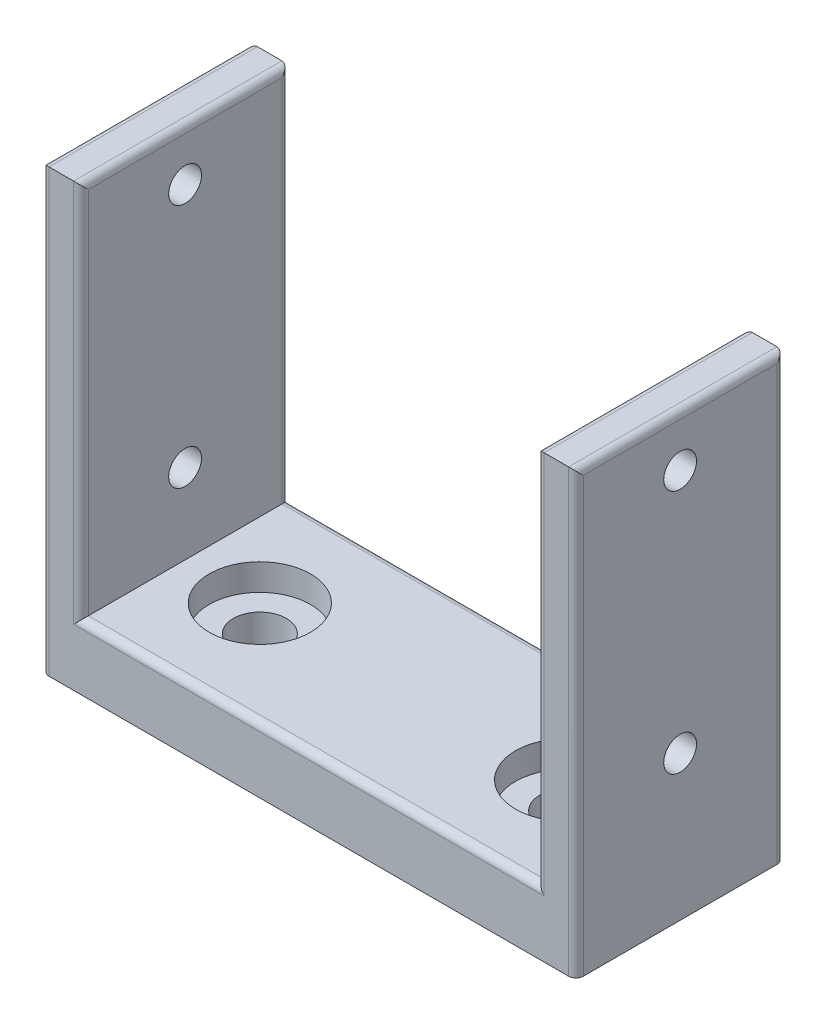
SolidWorks part; units mm, degrees
ref_plane "Front Plane" through (0, 0, 0) normal (0, 0, 1) x (1, 0, 0)
ref_plane "Top Plane" through (0, 0, 0) normal (0, 1, 0) x (1, 0, 0)
ref_plane "Right Plane" through (0, 0, 0) normal (1, 0, 0) x (0, 0, -1)
sketch "Sketch1" plane through (0, 0, 0) normal (0, 1, 0) x (1, 0, 0)
  line L1 (0, 21.59) -> (55.372, 21.59)
  line L2 (0, 21.59) -> (0, 0)
  line L3 (0, 0) -> (55.372, 0)
  line L4 (55.372, 21.59) -> (55.372, 0)
  dimension "D1" = 55.372
  dimension "D2" = 21.59
extrude "Boss-Extrude1" add sketch "Sketch1" along normal blind 4.16
sketch "Sketch2" plane through (0, 4.16, 0) normal (0, 1, 0) x (1, 0, 0)
  line L0 (0, 0) -> (55.372, 0) construction
  line L1 (0, 21.59) -> (4.064, 21.59)
  line L2 (0, 21.59) -> (0, 0)
  line L3 (0, 0) -> (4.064, 0)
  line L4 (4.064, 21.59) -> (4.064, 0)
  line L6 (55.372, 21.59) -> (51.308, 21.59)
  line L7 (55.372, 21.59) -> (55.372, 0)
  line L8 (55.372, 0) -> (51.308, 0)
  line L9 (51.308, 21.59) -> (51.308, 0)
  dimension "D1" = 4.064
  dimension "D2" = 4.064
extrude "Boss-Extrude2" add sketch "Sketch2" along normal blind 39.02
hole_wizard "M3 Clearance Hole2" positions "Sketch5" profile "Sketch4" hole size "M3" standard "ANSI Metric" end condition through all
sketch "Sketch5" plane through (0, 0, 0) normal (-1, 0, 0) x (0, 0, 1)
  line L0 (-21.59, 43.18) -> (0, 43.18) construction
  point P0 (-10.795, 37.86)
  point P2 (-10.795, 12.46)
  point P9 (-10.795, 43.18)
  dimension "D1" = 5.32
  dimension "D3" = 25.4
sketch "Sketch4" plane through (0, 37.86, -10.795) normal (0, 1, 0) x (0, 0, 1)
  line L0 (0, 0) -> (0, 55.372)
  line L1 (0, 55.372) -> (1.7, 55.372)
  line L2 (1.7, 55.372) -> (1.7, 0)
  line L5 (1.7, 0) -> (0, 0)
  line L11 (0, -6.35) -> (0, 107.95) construction
  dimension "Thru Hole Dia." = 3.4
  dimension "Thru Hole Depth" = 55.372
extrude "Boss-Extrude3" add sketch "Sketch1<2>" against normal blind 2.54
sketch "Sketch1<2>" plane through (0, 0, 0) normal (0, 1, 0) x (1, 0, 0) same geometry as "Sketch1"
sketch "Sketch6" plane through (0, 0, 0) normal (0, 0, 1) x (1, 0, 0)
  line L0 (0, -2.54) -> (55.372, -2.54) construction
  line L1 (4.064, -2.54) -> (51.308, -2.54)
  line L2 (4.064, -2.54) -> (4.064, 0)
  line L3 (4.064, 0) -> (51.308, 0)
  line L4 (51.308, -2.54) -> (51.308, 0)
  line L5 (4.064, 4.16) -> (51.308, 4.16) construction
  line L6 (4.064, 43.18) -> (4.064, 4.16) construction
  line L7 (51.308, 43.18) -> (51.308, 4.16) construction
  point P9 (27.686, 4.16)
  point P10 (27.686, 0)
  dimension "D1" = 2.54
extrude "Cut-Extrude1" [suppressed] cut sketch "Sketch6" against normal through all
ref_plane "Plane1" through (27.686, 0, 0) normal (1, 0, 0) x (0, 0, -1)
hole_wizard "CBORE for M5 SBHCS1" positions "Sketch7" profile "Sketch8" counterbore size "M5" standard "ANSI Metric" end condition through all
sketch "Sketch7" plane through (0, 4.16, 0) normal (0, 1, 0) x (1, 0, 0)
  line L0 (4.064, 0) -> (27.686, 0) construction
  line L1 (4.064, 0) -> (51.308, 0) construction
  line L3 (27.686, 21.59) -> (27.686, 0) construction
  line L4 (51.308, 21.59) -> (4.064, 21.59) construction
  point P0 (11.811, 10.795)
  point P2 (43.561, 10.795)
  point P19 (27.686, 10.795)
  dimension "D1" = 15.875
  dimension "D2" = 15.875
sketch "Sketch8" plane through (11.811, 4.16, -10.795) normal (1, 0, 0) x (0, 0, 1)
  line L0 (0, 0) -> (0, 6.7)
  line L1 (0, 6.7) -> (2.75, 6.7)
  line L3 (2.75, 6.7) -> (2.75, 2.75)
  line L4 (2.75, 2.75) -> (5.25, 2.75)
  line L5 (5.25, 2.75) -> (5.25, 0)
  line L7 (5.25, 0) -> (0, 0)
  line L11 (0, -6.35) -> (0, 107.95) construction
  dimension "Thru Hole Dia." = 5.5
  dimension "Thru Hole Depth" = 6.7
  dimension "C'Bore Dia." = 10.5
  dimension "C'Bore Depth" = 2.75
fillet "Fillet1" radius 0.762 14 edges at (4.064, 23.67, -21.59) (27.686, 4.16, -21.59) (51.308, 23.67, -21.59) (55.372, 20.32, -21.59) (51.308, 43.18, -10.795) (55.372, 43.18, -10.795) (27.686, 4.16, 0) (51.308, 23.67, 0) (55.372, 20.32, 0) (4.064, 43.18, -10.795) (0, 43.18, -10.795) (0, 20.32, -21.59) (0, 20.32, 0) (4.064, 23.67, 0)
